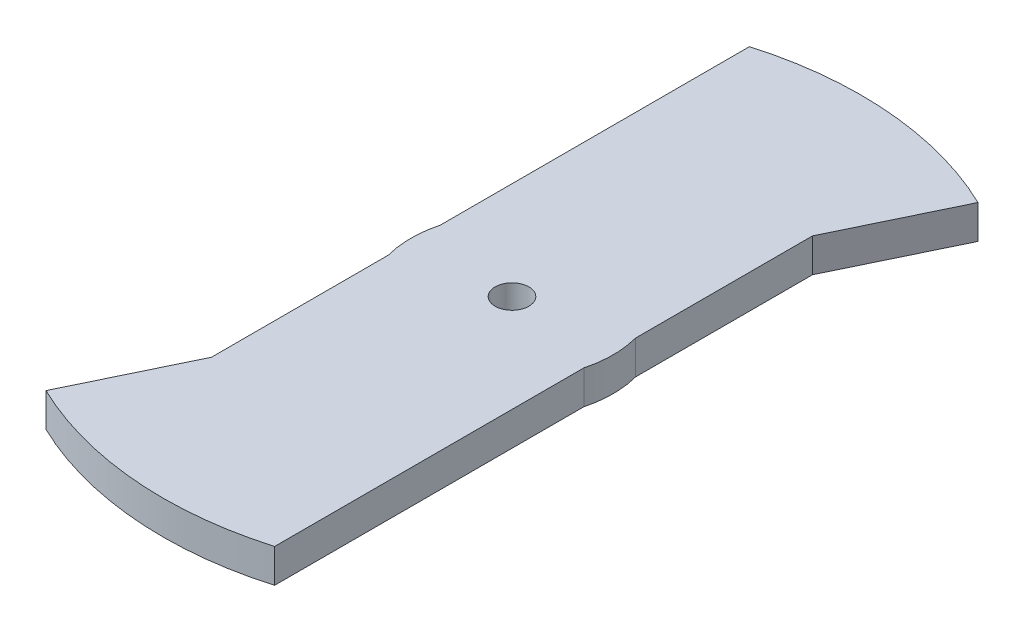
SolidWorks part; units mm, degrees
material "AISI 316 Stainless Steel Sheet (SS)"
ref_plane "Front Plane" through (0, 0, 0) normal (0, 0, 1) x (1, 0, 0)
ref_plane "Top Plane" through (0, 0, 0) normal (0, 1, 0) x (1, 0, 0)
ref_plane "Right Plane" through (0, 0, 0) normal (1, 0, 0) x (0, 0, -1)
sketch "Sketch1" plane through (0, 0, 0) normal (0, 1, 0) x (1, 0, 0)
  line L0 (0, 19.05) -> (0, 65.786) construction
  line L1 (-18.415, 63.156) -> (-18.415, 4.8775)
  line L2 (18.415, 4.8775) -> (18.415, 38.2122)
  line L3 (18.415, 38.2122) -> (28.5598, 59.2633)
  line L4 (18.415, -63.156) -> (18.415, -4.8775)
  line L5 (-18.415, -38.2122) -> (-28.5598, -59.2633)
  line L6 (-18.415, -4.8775) -> (-18.415, -38.2122)
  circle A0 centre (0, 0) radius 3.175
  circle A1 centre (0, 0) radius 19.05 construction
  circle A2 centre (0, 0) radius 65.786 construction
  arc A3 (-18.415, 63.156) -> (28.5598, 59.2633) centre (0, 0) cw
  circle A4 centre (0, 0) radius 42.418 construction
  arc A5 (18.415, -63.156) -> (-28.5598, -59.2633) centre (0, 0) cw
  arc A6 (-18.415, 4.8775) -> (-18.415, -4.8775) centre (0, 0) ccw
  arc A7 (18.415, 4.8775) -> (18.415, -4.8775) centre (0, 0) cw
  point P9 (18.415, 4.8775)
  point P15 (0, 42.418)
  point P23 (0, 0)
  dimension "D1" = 6.35
  dimension "D2" = 38.1
  dimension "D3" = 131.572
  dimension "D4" = 36.83
  dimension "D6" = 2
extrude "Boss-Extrude1" add sketch "Sketch1" along normal blind 6.35 contours A7 L2 L3 A3 L1 A6 L6 L5 A5 L4 A0 region at (5.3146, 0, -64.1318)
